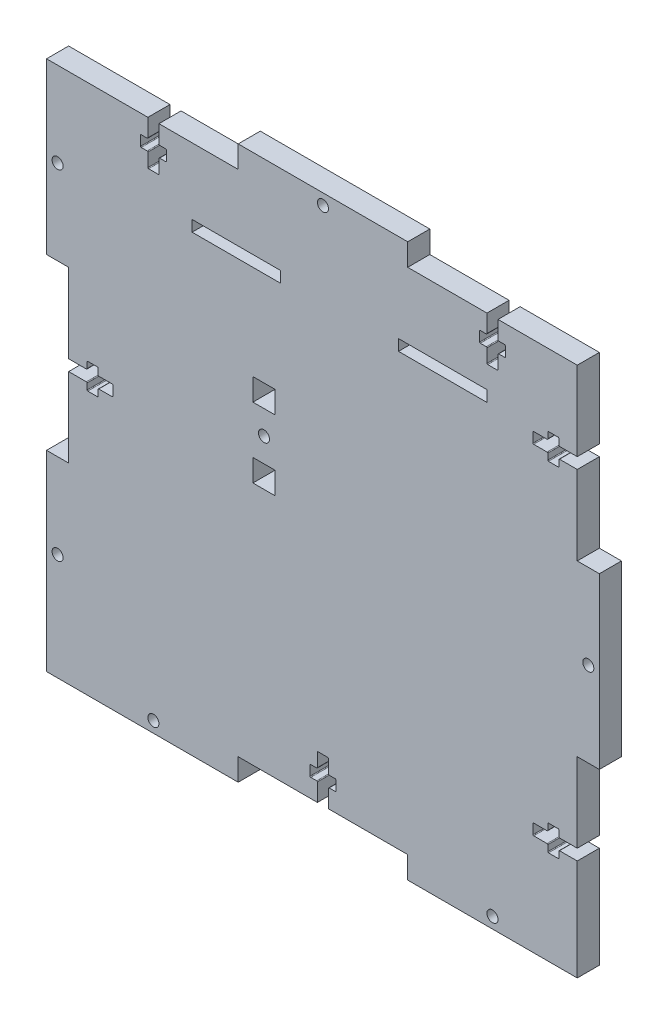
SolidWorks part; units mm, degrees
ref_plane "Front Plane" through (0, 0, 0) normal (0, 0, 1) x (1, 0, 0)
ref_plane "Top Plane" through (0, 0, 0) normal (0, 1, 0) x (1, 0, 0)
ref_plane "Right Plane" through (0, 0, 0) normal (1, 0, 0) x (0, 0, -1)
sketch "Sketch1" plane through (0, 0, 0) normal (0, 0, 1) x (1, 0, 0)
  line L0 (-69, 69) -> (-23, 69)
  line L5 (-75, -75) -> (75, -75) construction
  line L6 (-75, -75) -> (-75, 75) construction
  line L7 (-75, 75) -> (75, 75) construction
  line L8 (75, -75) -> (75, 75) construction
  line L9 (75, 23) -> (69, 23)
  line L10 (69, -23) -> (75, -23)
  line L11 (-69, -69) -> (69, -69) construction
  line L12 (-69, -69) -> (-69, 69) construction
  line L13 (-69, 69) -> (69, 69) construction
  line L14 (69, -69) -> (69, 69) construction
  line L15 (-69, -69) -> (69, 69) construction
  line L16 (69, -69) -> (69, -23)
  line L17 (-23, 69) -> (-23, 75)
  line L18 (-23, 75) -> (23, 75)
  line L19 (23, 75) -> (23, 69)
  line L20 (23, 69) -> (69, 69)
  line L21 (75, -23) -> (75, 23)
  line L22 (69, 23) -> (69, 69)
  line L23 (-75, 23) -> (-69, 23)
  line L24 (-69, 69) -> (-75, 69)
  line L25 (-75, 69) -> (-75, 23)
  line L26 (69, -69) -> (69, -75)
  line L27 (69, -75) -> (23, -75)
  line L28 (23, -75) -> (23, -69)
  line L29 (23, -69) -> (-23, -69)
  line L30 (-23, -69) -> (-23, -75)
  line L31 (-23, -75) -> (-69, -75)
  line L32 (-69, -75) -> (-69, -69) construction
  line L33 (-69, 23) -> (-69, -23)
  line L34 (-69, -23) -> (-75, -23)
  line L35 (-75, -23) -> (-75, -69)
  line L36 (-75, -69) -> (-69, -69) construction
  line L37 (-46, 69) -> (-46, -75) construction
  line L38 (-69, 69) -> (69, -69) construction
  line L39 (-75, -75) -> (-69, -75)
  line L40 (-75, -75) -> (-75, -69)
  point P0 (0, 0)
  point P6 (-7, -7)
  point P26 (0, -75)
  point P27 (-75, 0)
  dimension "D1" = 150
  dimension "D2" = 150
  dimension "D5" = 46
  dimension "D3" = 6
  dimension "D6" = 6
  dimension "D7" = 6
extrude "Box Side" add sketch "Sketch1" along normal blind 6
sketch "Sketch2" plane through (0, 0, 6) normal (0, 0, 1) x (1, 0, 0)
  line L0 (23, 72) -> (-23, 72) construction
  line L1 (23, 75) -> (23, 69) construction
  line L2 (-23, 69) -> (-23, 75) construction
  line L3 (-46, 69) -> (-46, -75) construction
  line L5 (0, 75) -> (0, 69) construction
  line L6 (-23, 75) -> (23, 75) construction
  line L7 (-69, 69) -> (69, 69) construction
  line L16 (-46, 69) -> (-46, -75) construction
  line L21 (0, -69) -> (0, 69) construction
  line L35 (-69, 69) -> (-23, 69) construction
  line L36 (-44.5, 69) -> (-44.5, 64.2)
  line L37 (-44.3, 64) -> (-42.7, 64)
  line L38 (-42.5, 63.8) -> (-42.5, 61.2)
  line L39 (-42.7, 61) -> (-44.3, 61)
  line L40 (-44.5, 60.8) -> (-44.5, 57.2)
  line L46 (-44.7, 57) -> (-47.3, 57)
  line L48 (-44.5, 69) -> (-47.5, 69)
  line L51 (-47.5, 60.8) -> (-47.5, 57.2)
  line L52 (-49.3, 61) -> (-47.7, 61)
  line L53 (-49.5, 63.8) -> (-49.5, 61.2)
  line L54 (-47.7, 64) -> (-49.3, 64)
  line L55 (-47.5, 69) -> (-47.5, 64.2)
  line L56 (47.5, 69) -> (47.5, 64.2)
  line L57 (47.7, 64) -> (49.3, 64)
  line L58 (49.5, 63.8) -> (49.5, 61.2)
  line L59 (49.3, 61) -> (47.7, 61)
  line L60 (47.5, 60.8) -> (47.5, 57.2)
  line L61 (44.5, 69) -> (47.5, 69)
  line L62 (44.7, 57) -> (47.3, 57)
  line L63 (44.5, 60.8) -> (44.5, 57.2)
  line L64 (42.7, 61) -> (44.3, 61)
  line L65 (42.5, 63.8) -> (42.5, 61.2)
  line L66 (44.3, 64) -> (42.7, 64)
  line L67 (44.5, 69) -> (44.5, 64.2)
  line L68 (-69, -69) -> (69, 69) construction
  line L69 (-69, -69) -> (69, 69) construction
  line L70 (75, 0) -> (69, 0) construction
  line L71 (72, 23) -> (72, -23) construction
  line L72 (69, 44.5) -> (64.2, 44.5)
  line L73 (64, 44.3) -> (64, 42.7)
  line L74 (63.8, 42.5) -> (61.2, 42.5)
  line L75 (61, 42.7) -> (61, 44.3)
  line L76 (60.8, 44.5) -> (57.2, 44.5)
  line L77 (57, 44.7) -> (57, 47.3)
  line L78 (69, 44.5) -> (69, 47.5)
  line L79 (60.8, 47.5) -> (57.2, 47.5)
  line L80 (61, 49.3) -> (61, 47.7)
  line L81 (63.8, 49.5) -> (61.2, 49.5)
  line L82 (64, 47.7) -> (64, 49.3)
  line L83 (69, 47.5) -> (64.2, 47.5)
  line L84 (69, -47.5) -> (64.2, -47.5)
  line L85 (64, -47.7) -> (64, -49.3)
  line L86 (63.8, -49.5) -> (61.2, -49.5)
  line L87 (61, -49.3) -> (61, -47.7)
  line L88 (60.8, -47.5) -> (57.2, -47.5)
  line L89 (69, -44.5) -> (69, -47.5)
  line L90 (57, -44.7) -> (57, -47.3)
  line L91 (60.8, -44.5) -> (57.2, -44.5)
  line L92 (61, -42.7) -> (61, -44.3)
  line L93 (63.8, -42.5) -> (61.2, -42.5)
  line L94 (64, -44.3) -> (64, -42.7)
  line L95 (69, -44.5) -> (64.2, -44.5)
  line L120 (-69, 69) -> (69, -69) construction
  line L121 (-69, 69) -> (69, -69) construction
  line L122 (-1.5, -69) -> (1.5, -69)
  line L123 (-23, -69) -> (23, -69) construction
  line L124 (1.5, -69) -> (1.5, -64.2)
  line L125 (1.7, -64) -> (3.3, -64)
  line L126 (3.5, -63.8) -> (3.5, -61.2)
  line L127 (3.3, -61) -> (1.7, -61)
  line L128 (1.5, -60.8) -> (1.5, -57.2)
  line L129 (1.3, -57) -> (-1.3, -57)
  line L130 (-1.5, -60.8) -> (-1.5, -57.2)
  line L131 (-3.3, -61) -> (-1.7, -61)
  line L132 (-3.5, -63.8) -> (-3.5, -61.2)
  line L133 (-1.7, -64) -> (-3.3, -64)
  line L134 (-1.5, -69) -> (-1.5, -64.2)
  line L135 (-69, -1.5) -> (-64.2, -1.5)
  line L136 (-64, -1.7) -> (-64, -3.3)
  line L137 (-63.8, -3.5) -> (-61.2, -3.5)
  line L138 (-61, -3.3) -> (-61, -1.7)
  line L139 (-60.8, -1.5) -> (-57.2, -1.5)
  line L140 (-57, 1.3) -> (-57, -1.3)
  line L141 (-60.8, 1.5) -> (-57.2, 1.5)
  line L142 (-61, 3.3) -> (-61, 1.7)
  line L143 (-63.8, 3.5) -> (-61.2, 3.5)
  line L144 (-64, 1.7) -> (-64, 3.3)
  line L145 (-69, 1.5) -> (-64.2, 1.5)
  line L146 (-69, -1.5) -> (-69, 1.5)
  line L147 (-69, -72) -> (-23, -72) construction
  line L148 (-23, 69) -> (-75, 69) construction
  line L149 (-23, -75) -> (-23, -69) construction
  line L150 (-69, -69) -> (-69, -75) construction
  line L151 (-75, -75) -> (-23, -75) construction
  circle A0 centre (0, 72) radius 1.5
  arc A1 (-44.5, 57.2) -> (-44.7, 57) centre (-44.7, 57.2) cw
  arc A2 (-44.3, 61) -> (-44.5, 60.8) centre (-44.3, 60.8) ccw
  arc A3 (-42.5, 61.2) -> (-42.7, 61) centre (-42.7, 61.2) cw
  arc A4 (-42.7, 64) -> (-42.5, 63.8) centre (-42.7, 63.8) cw
  arc A5 (-44.5, 64.2) -> (-44.3, 64) centre (-44.3, 64.2) ccw
  arc A6 (-47.5, 64.2) -> (-47.7, 64) centre (-47.7, 64.2) cw
  arc A7 (-49.3, 64) -> (-49.5, 63.8) centre (-49.3, 63.8) ccw
  arc A8 (-49.5, 61.2) -> (-49.3, 61) centre (-49.3, 61.2) ccw
  arc A9 (-47.7, 61) -> (-47.5, 60.8) centre (-47.7, 60.8) cw
  arc A10 (-47.5, 57.2) -> (-47.3, 57) centre (-47.3, 57.2) ccw
  arc A11 (47.5, 57.2) -> (47.3, 57) centre (47.3, 57.2) cw
  arc A12 (47.7, 61) -> (47.5, 60.8) centre (47.7, 60.8) ccw
  arc A13 (49.5, 61.2) -> (49.3, 61) centre (49.3, 61.2) cw
  arc A14 (49.3, 64) -> (49.5, 63.8) centre (49.3, 63.8) cw
  arc A15 (47.5, 64.2) -> (47.7, 64) centre (47.7, 64.2) ccw
  arc A16 (44.5, 64.2) -> (44.3, 64) centre (44.3, 64.2) cw
  arc A17 (42.7, 64) -> (42.5, 63.8) centre (42.7, 63.8) ccw
  arc A18 (42.5, 61.2) -> (42.7, 61) centre (42.7, 61.2) ccw
  arc A19 (44.3, 61) -> (44.5, 60.8) centre (44.3, 60.8) cw
  arc A20 (44.5, 57.2) -> (44.7, 57) centre (44.7, 57.2) ccw
  arc A21 (57.2, 44.5) -> (57, 44.7) centre (57.2, 44.7) cw
  arc A22 (61, 44.3) -> (60.8, 44.5) centre (60.8, 44.3) ccw
  arc A23 (61.2, 42.5) -> (61, 42.7) centre (61.2, 42.7) cw
  arc A24 (64, 42.7) -> (63.8, 42.5) centre (63.8, 42.7) cw
  arc A25 (64.2, 44.5) -> (64, 44.3) centre (64.2, 44.3) ccw
  arc A26 (64.2, 47.5) -> (64, 47.7) centre (64.2, 47.7) cw
  arc A27 (64, 49.3) -> (63.8, 49.5) centre (63.8, 49.3) ccw
  arc A28 (61.2, 49.5) -> (61, 49.3) centre (61.2, 49.3) ccw
  arc A29 (61, 47.7) -> (60.8, 47.5) centre (60.8, 47.7) cw
  arc A30 (57.2, 47.5) -> (57, 47.3) centre (57.2, 47.3) ccw
  arc A31 (57.2, -47.5) -> (57, -47.3) centre (57.2, -47.3) cw
  arc A32 (61, -47.7) -> (60.8, -47.5) centre (60.8, -47.7) ccw
  arc A33 (61.2, -49.5) -> (61, -49.3) centre (61.2, -49.3) cw
  arc A34 (64, -49.3) -> (63.8, -49.5) centre (63.8, -49.3) cw
  arc A35 (64.2, -47.5) -> (64, -47.7) centre (64.2, -47.7) ccw
  arc A36 (64.2, -44.5) -> (64, -44.3) centre (64.2, -44.3) cw
  arc A37 (64, -42.7) -> (63.8, -42.5) centre (63.8, -42.7) ccw
  arc A38 (61.2, -42.5) -> (61, -42.7) centre (61.2, -42.7) ccw
  arc A39 (61, -44.3) -> (60.8, -44.5) centre (60.8, -44.3) cw
  arc A40 (57.2, -44.5) -> (57, -44.7) centre (57.2, -44.7) ccw
  circle A41 centre (72, 0) radius 1.5
  arc A62 (1.5, -57.2) -> (1.3, -57) centre (1.3, -57.2) ccw
  arc A63 (1.7, -61) -> (1.5, -60.8) centre (1.7, -60.8) cw
  arc A64 (3.5, -61.2) -> (3.3, -61) centre (3.3, -61.2) ccw
  arc A65 (3.3, -64) -> (3.5, -63.8) centre (3.3, -63.8) ccw
  arc A66 (1.5, -64.2) -> (1.7, -64) centre (1.7, -64.2) cw
  arc A67 (-1.5, -64.2) -> (-1.7, -64) centre (-1.7, -64.2) ccw
  arc A68 (-3.3, -64) -> (-3.5, -63.8) centre (-3.3, -63.8) cw
  arc A69 (-3.5, -61.2) -> (-3.3, -61) centre (-3.3, -61.2) cw
  arc A70 (-1.7, -61) -> (-1.5, -60.8) centre (-1.7, -60.8) ccw
  arc A71 (-1.5, -57.2) -> (-1.3, -57) centre (-1.3, -57.2) cw
  arc A72 (-57.2, -1.5) -> (-57, -1.3) centre (-57.2, -1.3) ccw
  arc A73 (-61, -1.7) -> (-60.8, -1.5) centre (-60.8, -1.7) cw
  arc A74 (-61.2, -3.5) -> (-61, -3.3) centre (-61.2, -3.3) ccw
  arc A75 (-64, -3.3) -> (-63.8, -3.5) centre (-63.8, -3.3) ccw
  arc A76 (-64.2, -1.5) -> (-64, -1.7) centre (-64.2, -1.7) cw
  arc A77 (-64.2, 1.5) -> (-64, 1.7) centre (-64.2, 1.7) ccw
  arc A78 (-64, 3.3) -> (-63.8, 3.5) centre (-63.8, 3.3) cw
  arc A79 (-61.2, 3.5) -> (-61, 3.3) centre (-61.2, 3.3) cw
  arc A80 (-61, 1.7) -> (-60.8, 1.5) centre (-60.8, 1.7) ccw
  arc A81 (-57.2, 1.5) -> (-57, 1.3) centre (-57.2, 1.3) cw
  circle A82 centre (-46, -72) radius 1.5
  circle A83 centre (46, -72) radius 1.5
  circle A84 centre (-72, 46) radius 1.5
  circle A85 centre (-72, -46) radius 1.5
  point P6 (0, 72)
  point P38 (0, 0)
  point P56 (-46, 57)
  point P88 (46, 57)
  point P161 (57, 46)
  point P162 (57, -46)
  point P198 (0, -57)
  point P231 (-57, 0)
  point P234 (-42.5, 62.5)
  dimension "D1" = 3
  dimension "D2" = 0.2
  dimension "D8" = 0.2
  dimension "D14" = 3
  dimension "D4" = 3
  dimension "D7" = 1.5
  dimension "D10" = 3
  dimension "D12" = 1.5
  dimension "D9" = 12
  dimension "D11" = 5
  dimension "D13" = 7
  dimension "D3" = 12
  dimension "D5" = 7
  dimension "D6" = 5
extrude "Screw Cut-outs" cut sketch "Sketch2" against normal through all
sketch "Sketch3" plane through (0, 0, 6) normal (0, 0, 1) x (1, 0, 0)
  line L0 (69, 23) -> (69, 44.5) construction
  line L1 (44.5, 51) -> (20.5, 51)
  line L2 (44.5, 51) -> (44.5, 48)
  line L3 (44.5, 48) -> (20.5, 48)
  line L4 (20.5, 51) -> (20.5, 48)
  line L5 (44.5, 69) -> (23, 69) construction
  line L6 (75, -23) -> (75, 23) construction
  line L7 (-13, 22.32) -> (-19, 22.32)
  line L8 (-13, 22.32) -> (-13, 16.32)
  line L9 (-13, 16.32) -> (-19, 16.32)
  line L10 (-19, 22.32) -> (-19, 16.32)
  line L11 (-13, 3.32) -> (-19, 3.32)
  line L12 (-13, 3.32) -> (-13, -2.68)
  line L13 (-13, -2.68) -> (-19, -2.68)
  line L14 (-19, 3.32) -> (-19, -2.68)
  line L15 (-23, -69) -> (-1.5, -69) construction
  line L16 (-16, 3.32) -> (-16, 16.32) construction
  line L18 (-11.5, 51) -> (-35.5, 51)
  line L19 (-11.5, 51) -> (-11.5, 48)
  line L20 (-11.5, 48) -> (-35.5, 48)
  line L21 (-35.5, 51) -> (-35.5, 48)
  circle A0 centre (-16, 9.82) radius 1.5
  point P22 (-16, 16.32)
  point P27 (-16, 9.82)
  dimension "D9" = 3
  dimension "D1" = 3
  dimension "D2" = 24.5
  dimension "D3" = 24
  dimension "D4" = 18
  dimension "D5" = 6
  dimension "D6" = 88
  dimension "D7" = 66.32
  dimension "D8" = 13
  dimension "D10" = 32
extrude "Grooves" cut sketch "Sketch3" against normal through all
equation "\"filletRadius\"=0.2"
equation "\"D8@Sketch2\"=\"filletRadius\""
equation "\"D2@Sketch2\"=\"filletRadius\""
equation "\"fingerWidth\"= 46"
equation "\"D5@Sketch1\"=\"fingerWidth\""
equation "\"wallThickness\"= 6"
equation "\"D3@Sketch1\" = \"wallThickness\""
equation "\"D6@Sketch1\" = \"wallThickness\""
equation "\"D7@Sketch1\" = \"wallThickness\""
equation "\"D1@Box Side\" = \"wallThickness\""
equation "\"M3\"= 3"
equation "\"D14@Sketch2\"=\"M3\""
equation "\"D1@Sketch2\"=\"M3\""
equation "\"D12@Sketch2\"=\"M3\"/2"
equation "\"nutThickness\"=3"
equation "\"D10@Sketch2\" = \"nutThickness\""
equation "\"boltLength\"= 12"
equation "\"D9@Sketch2\" = \"boltLength\""
equation "\"distanceToNut\"= 5"
equation "\"D11@Sketch2\" = \"distanceToNut\""
equation "\"D13@Sketch2\" = \"nutWidth\""
equation "\"D7@Sketch2\"=\"M3\"/2"
equation "\"D4@Sketch2\" = \"nutThickness\""
equation "\"D3@Sketch2\" = \"boltLength\""
equation "\"D5@Sketch2\" = \"nutWidth\""
equation "\"D6@Sketch2\" = \"distanceToNut\""
equation "\"sideLength\"=150"
equation "\"D1@Sketch1\"=\"sideLength\""
equation "\"D2@Sketch1\"=\"sideLength\""
equation "\"nutWidth\"=7"
